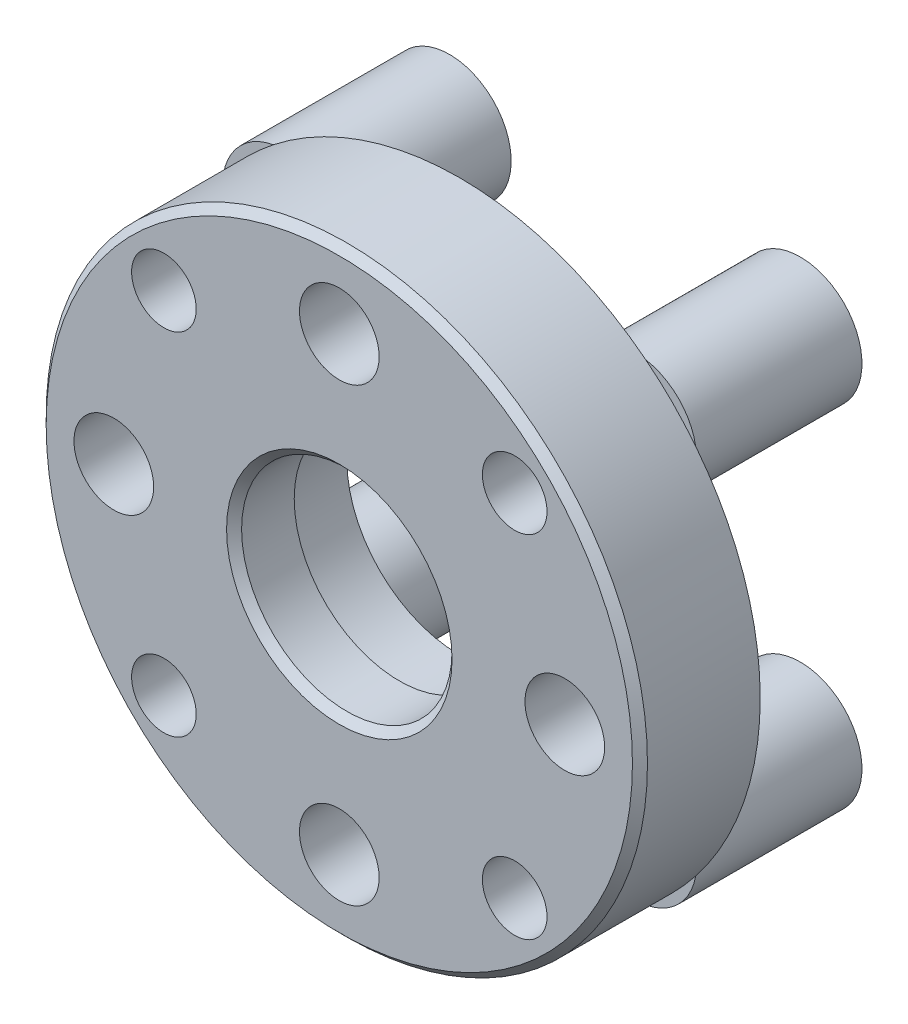
SolidWorks part; units mm, degrees
material "ABS"
ref_plane "Front Plane" through (0, 0, 0) normal (0, 0, 1) x (1, 0, 0)
ref_plane "Top Plane" through (0, 0, 0) normal (0, 1, 0) x (1, 0, 0)
ref_plane "Right Plane" through (0, 0, 0) normal (1, 0, 0) x (0, 0, -1)
ref_plane "Output Plane" through (0, 0, 24.3786) normal (0, 0, -1) x (-1, 0, 0)
sketch "CYC Output Sketch" plane through (0, 0, 24.3786) normal (0, 0, 1) x (1, 0, 0)
  line L1 (11.6673, 11.6673) -> (-11.6673, 11.6673) construction
  line L2 (-11.6673, 11.6673) -> (-11.6673, -11.6673) construction
  line L3 (-11.6673, -11.6673) -> (11.6673, -11.6673) construction
  line L4 (11.6673, -11.6673) -> (11.6673, 11.6673) construction
  circle A0 centre (0, 0) radius 16.5 construction
sketch "Sketch3" plane through (0, 0, 24.3786) normal (0, 0, -1) x (-1, 0, 0)
  circle A0 centre (-11.6673, 11.6673) radius 4
  circle A1 centre (11.6673, 11.6673) radius 4
  circle A2 centre (11.6673, -11.6673) radius 4
  circle A3 centre (-11.6673, -11.6673) radius 4
  dimension "D1" = 8
extrude "Boss-Extrude1" add sketch "Sketch3" along normal blind 11
sketch "Sketch6" plane through (0, 0, 24.3786) normal (0, 0, 1) x (1, 0, 0)
  arc A0 (10.6823, 16.9082) -> (-16.9082, 10.6823) centre (0, 0) ccw
  arc A18 (16.9082, -10.6823) -> (10.6823, 16.9082) centre (0, 0) ccw
  arc A19 (-10.6823, -16.9082) -> (16.9082, -10.6823) centre (0, 0) ccw
  arc A20 (-16.9082, 10.6823) -> (-10.6823, -16.9082) centre (0, 0) ccw
  circle A23 centre (0, 0) radius 7.5
  dimension "D2" = 40
  dimension "D1" = 15
extrude "Boss-Extrude6" add sketch "Sketch6" along normal blind 8 contours A23 | A0 A20 A19 A18 region at (0, 0, 24.3786)
sketch "Sketch8" plane through (0, 0, 32.3786) normal (0, 0, 1) x (1, 0, 0)
  line L0 (0, 0) -> (11.6673, 11.6673) construction
  line L1 (0, 0) -> (16.5, 0) construction
  circle A0 centre (0, 0) radius 16.5 construction
  circle A1 centre (11.6673, 11.6673) radius 1.6
  circle A2 centre (11.6673, -11.6673) radius 1.6
  circle A3 centre (-11.6673, -11.6673) radius 1.6
  circle A4 centre (-11.6673, 11.6673) radius 1.6
  point P16 (0, 0)
  dimension "D1" = 33
  dimension "D2" = 45
  dimension "D3" = 3.2
  dimension "D4" = 4
extrude "Cut-Extrude1" cut sketch "Sketch8" against normal through all
sketch "Sketch9" plane through (0, 0, 13.3786) normal (0, 0, 1) x (1, 0, 0)
  circle A0 centre (11.6673, 11.6673) radius 3
  circle A1 centre (11.6673, -11.6673) radius 3
  circle A2 centre (-11.6673, -11.6673) radius 3
  circle A3 centre (-11.6673, 11.6673) radius 3
  point P12 (0, 0)
  dimension "D1" = 6
  dimension "D2" = 4
extrude "Cut-Extrude2" cut sketch "Sketch9" along normal blind 3 from surface starting at face at (13.2673, 11.6673, 13.3786)
sketch "Sketch10" plane through (0, 0, 13.3786) normal (0, 0, -1) x (-1, 0, 0)
  circle A0 centre (11.6673, 11.6673) radius 4.1
  circle A1 centre (11.6673, 11.6673) radius 4
  circle A2 centre (11.6673, -11.6673) radius 4
  circle A3 centre (11.6673, -11.6673) radius 4.1
  circle A4 centre (-11.6673, -11.6673) radius 4
  circle A5 centre (-11.6673, -11.6673) radius 4.1
  circle A6 centre (-11.6673, 11.6673) radius 4
  circle A7 centre (-11.6673, 11.6673) radius 4.1
  point P16 (0, 0)
  dimension "D1" = 8
  dimension "D2" = 8.2
  dimension "D3" = 4
extrude "Boss-Extrude8" add sketch "Sketch10" against normal blind 11
sketch "Sketch11" plane through (0, 0, 32.3786) normal (0, 0, 1) x (1, 0, 0)
  line L0 (0, 0) -> (0, 15) construction
  circle A0 centre (0, 15) radius 2.65
  circle A1 centre (15, 0) radius 2.65
  circle A2 centre (0, -15) radius 2.65
  circle A3 centre (-15, 0) radius 2.65
  circle A4 centre (-11.6673, 11.6673) radius 2.15
  circle A5 centre (11.6673, 11.6673) radius 2.15
  circle A6 centre (11.6673, -11.6673) radius 2.15
  circle A7 centre (-11.6673, -11.6673) radius 2.15
  point P13 (0, 0)
  dimension "D2" = 5.3
  dimension "D4" = 4.3
  dimension "D1" = 15
  dimension "D3" = 4
extrude "Cut-Extrude3" cut sketch "Sketch11" against normal blind 8
sketch "Sketch12" plane through (0, 0, 32.3786) normal (0, 0, 1) x (1, 0, 0)
  circle A0 centre (0, 0) radius 7.5
  circle A1 centre (0, 0) radius 7
  dimension "D1" = 15
  dimension "D2" = 14
extrude "Boss-Extrude9" add sketch "Sketch12" against normal blind 4
chamfer "Chamfer1" distance 0.5 angle 45 2 edges at (7, 0, 32.3786) (20, 0, 32.3786)
equation "\"RingPinShaft\"= 5.05"
equation "\"CenterBearingOut\"=32.00"
equation "\"RingPostIn\"=5.15"
equation "\"CamBearingOut\"=15.1"
equation "\"DiskOutputShaft\"=10.1"
equation "\"CenterShaft\"=25.2"
equation "\"Eccentricity\"=2"
equation "\"CycCamShaft\"=10.05"
equation "\"D2@Sketch6\"=\"OutputBearing\""
equation "\"OutputBearing\"=40"
